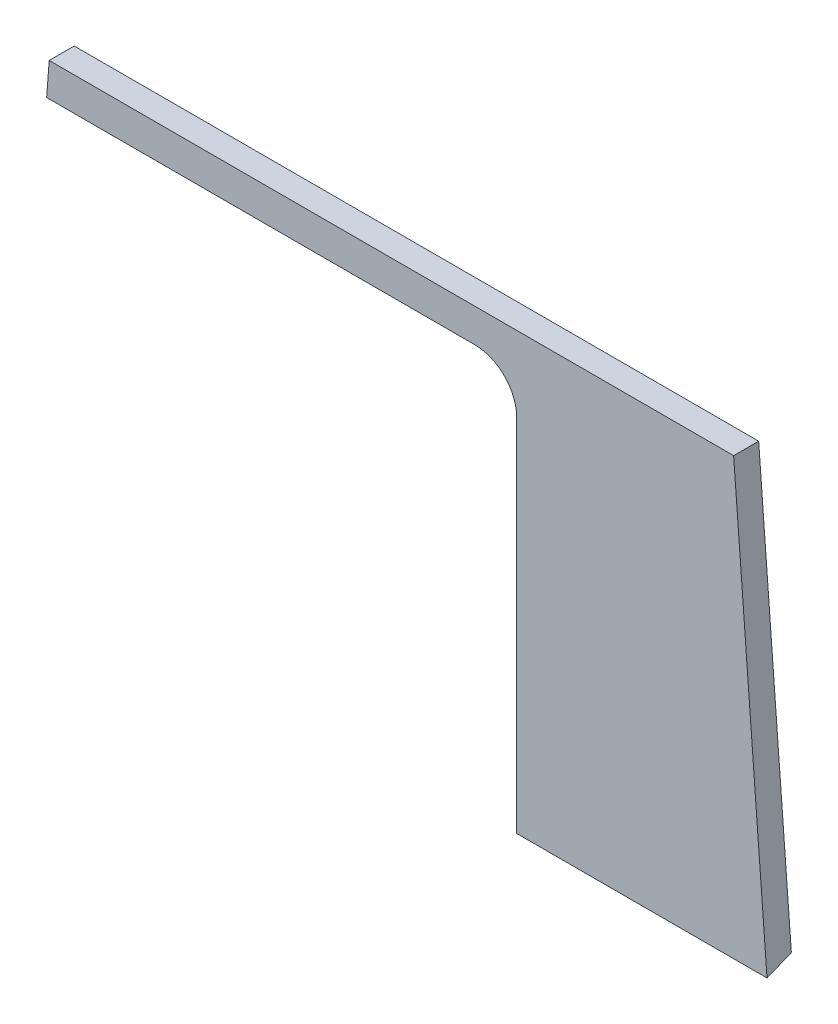
SolidWorks part; units mm, degrees
material "Acrylic (Medium-high impact)"
ref_plane "Front Plane" through (0, 0, 0) normal (0, 0, 1) x (1, 0, 0)
ref_plane "Top Plane" through (0, 0, 0) normal (0, 1, 0) x (1, 0, 0)
ref_plane "Right Plane" through (0, 0, 0) normal (1, 0, 0) x (0, 0, -1)
sketch "Sketch1" plane through (0, 0, 0) normal (0, 0, 1) x (1, 0, 0)
  line L0 (-45, 0) -> (45, 0)
  line L1 (-45, 0) -> (-41, 52.2)
  line L2 (-41, 52.2) -> (41, 52.2)
  line L3 (41, 52.2) -> (45, 0)
  point P0 (0, 52.2)
  point P4 (0, 0)
  dimension "D1" = 90
  dimension "D2" = 52.2
  dimension "D3" = 82
extrude "Boss-Extrude1" add sketch "Sketch1" along normal mid plane 3
chamfer "Chamfer1" distance 3 angle 20 1 edges at (0, 0, -1.5) first distance on face at (0, 0, 0)
sketch "Sketch2" [suppressed] plane through (0, 0, 1.5) normal (0, 0, 1) x (1, 0, 0)
  line L0 (-45, 0) -> (45, 0) construction
  line L1 (-42.9941, 0) -> (42.9941, 0)
  line L2 (-42.9941, 0) -> (-41.8481, 14.9562)
  line L3 (-41.8481, 14.9562) -> (41.8481, 14.9562)
  line L4 (42.9941, 0) -> (41.8481, 14.9562)
  line L5 (45, 0) -> (41, 52.2) construction
  line L6 (-41, 52.2) -> (-45, 0) construction
  dimension "D1" = 15
  dimension "D2" = 2
  dimension "D3" = 2
extrude "Cut-Extrude1" [suppressed] cut sketch "Sketch2" against normal through all
sketch "Sketch3" plane through (0, 0, 1.5) normal (0, 0, 1) x (1, 0, 0)
  line L0 (41, 52.2) -> (-41, 52.2) construction
  line L1 (-45, 0) -> (15, 0)
  line L2 (-45, 0) -> (-45, 48.2)
  line L3 (-45, 48.2) -> (15, 48.2)
  line L4 (15, 0) -> (15, 48.2)
  dimension "D1" = 4
  dimension "D2" = 60
extrude "Cut-Extrude2" cut sketch "Sketch3" against normal through all
fillet "Fillet1" radius 5 1 edges at (15, 48.2, 0)
equation "\"D2@Sketch2\"=\"D3@Sketch2\""
